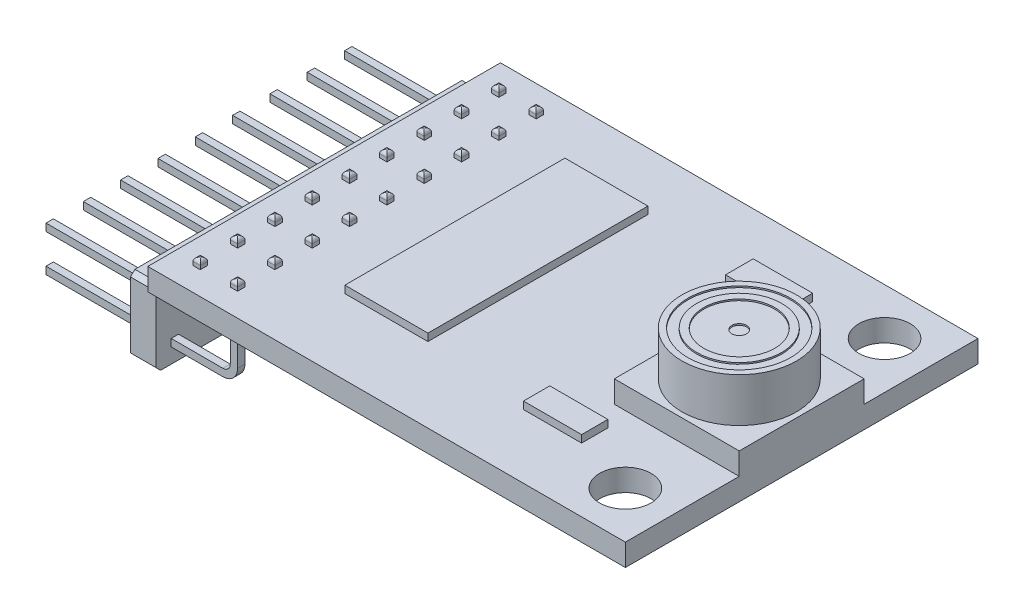
SolidWorks part; units mm, degrees
ref_plane "前视基准面" through (0, 0, 0) normal (0, 0, 1) x (1, 0, 0)
ref_plane "上视基准面" through (0, 0, 0) normal (0, 1, 0) x (1, 0, 0)
ref_plane "右视基准面" through (0, 0, 0) normal (1, 0, 0) x (0, 0, -1)
other "Configuration Table"
sketch "草图1" plane through (0, 0, 0) normal (0, 1, 0) x (1, 0, 0)
  line L0 (0, -12) -> (32.5, -12) construction
  line L1 (0, 0) -> (32.5, 0)
  line L2 (0, 0) -> (0, -24)
  line L3 (0, -24) -> (32.5, -24)
  line L4 (32.5, 0) -> (32.5, -24)
  circle A0 centre (29.32, -3.18) radius 1.75
  circle A1 centre (29.32, -20.82) radius 1.75
  dimension "D3" = 3.5
  dimension "D4" = 3.18
  dimension "D5" = 3.18
  dimension "D6" = 3.5
  dimension "D7" = 3.18
  dimension "D8" = 3.18
  dimension "D1" = 24
  dimension "D2" = 32.5
extrude "凸台-拉伸1" add sketch "草图1" along normal blind 1.5
sketch "草图2" plane through (0, 1.5, 0) normal (0, 1, 0) x (1, 0, 0)
  line L0 (0, -12) -> (32.5, -12) construction
  line L1 (0, 0) -> (0, -24) construction
  line L2 (32.5, -24) -> (32.5, 0) construction
  line L4 (24, -7.75) -> (32.5, -7.75)
  line L5 (24, -7.75) -> (24, -16.25)
  line L6 (24, -16.25) -> (32.5, -16.25)
  line L7 (32.5, -7.75) -> (32.5, -16.25)
  line L8 (24, -7.75) -> (32.5, -16.25) construction
  line L9 (24, -16.25) -> (32.5, -7.75) construction
  point P6 (28.25, -12)
  dimension "D1" = 8.5
  dimension "D2" = 8.5
extrude "凸台-拉伸2" add sketch "草图2" along normal blind 1.5
sketch "草图3" plane through (0, 3, 0) normal (0, 1, 0) x (1, 0, 0)
  line L0 (24, -12) -> (32.5, -12) construction
  line L1 (24, -7.75) -> (24, -16.25) construction
  line L2 (32.5, -16.25) -> (32.5, -7.75) construction
  line L3 (28.25, -7.75) -> (28.25, -16.25) construction
  line L4 (32.5, -7.75) -> (24, -7.75) construction
  line L5 (24, -16.25) -> (32.5, -16.25) construction
  circle A0 centre (28.25, -12) radius 3.9
  dimension "D1" = 7.8
extrude "凸台-拉伸3" add sketch "草图3" along normal blind 3
sketch "草图4" plane through (0, 0, 0) normal (0, -1, 0) x (1, 0, 0)
  line L0 (1.73, 0) -> (1.73, 24) construction
  line L1 (32.5, 0) -> (0, 0) construction
  line L2 (0, 24) -> (32.5, 24) construction
  line L3 (4.27, 0) -> (4.27, 24) construction
  line L4 (0, 0) -> (0, 24) construction
  line L5 (0, 12) -> (32.5, 12) construction
  line L6 (32.5, 24) -> (32.5, 0) construction
  line L7 (1.48, 14.79) -> (1.98, 14.79)
  line L8 (1.48, 12.25) -> (1.98, 12.25)
  line L9 (1.48, 12.25) -> (1.48, 11.75)
  line L10 (1.48, 11.75) -> (1.98, 11.75)
  line L11 (1.98, 12.25) -> (1.98, 11.75)
  line L12 (1.48, 12.25) -> (1.98, 11.75) construction
  line L13 (1.48, 11.75) -> (1.98, 12.25) construction
  line L14 (4.02, 12.25) -> (4.52, 12.25)
  line L15 (4.02, 12.25) -> (4.02, 11.75)
  line L16 (4.02, 11.75) -> (4.52, 11.75)
  line L17 (4.52, 12.25) -> (4.52, 11.75)
  line L18 (4.02, 12.25) -> (4.52, 11.75) construction
  line L19 (4.02, 11.75) -> (4.52, 12.25) construction
  line L20 (1.48, 14.79) -> (1.48, 14.29)
  line L21 (1.98, 14.79) -> (1.98, 14.29)
  line L22 (1.48, 14.29) -> (1.98, 14.29)
  line L23 (4.02, 14.29) -> (4.52, 14.29)
  line L24 (4.52, 14.79) -> (4.52, 14.29)
  line L25 (4.02, 14.79) -> (4.02, 14.29)
  line L26 (4.02, 14.79) -> (4.52, 14.79)
  line L27 (1.48, 17.33) -> (1.98, 17.33)
  line L28 (1.48, 17.33) -> (1.48, 16.83)
  line L29 (1.98, 17.33) -> (1.98, 16.83)
  line L30 (1.48, 16.83) -> (1.98, 16.83)
  line L31 (4.02, 16.83) -> (4.52, 16.83)
  line L32 (4.52, 17.33) -> (4.52, 16.83)
  line L33 (4.02, 17.33) -> (4.02, 16.83)
  line L34 (4.02, 17.33) -> (4.52, 17.33)
  line L35 (1.48, 19.87) -> (1.98, 19.87)
  line L36 (1.48, 19.87) -> (1.48, 19.37)
  line L37 (1.98, 19.87) -> (1.98, 19.37)
  line L38 (1.48, 19.37) -> (1.98, 19.37)
  line L39 (4.02, 19.37) -> (4.52, 19.37)
  line L40 (4.52, 19.87) -> (4.52, 19.37)
  line L41 (4.02, 19.87) -> (4.02, 19.37)
  line L42 (4.02, 19.87) -> (4.52, 19.87)
  line L43 (1.48, 22.41) -> (1.98, 22.41)
  line L44 (1.48, 22.41) -> (1.48, 21.91)
  line L45 (1.98, 22.41) -> (1.98, 21.91)
  line L46 (1.48, 21.91) -> (1.98, 21.91)
  line L47 (4.02, 21.91) -> (4.52, 21.91)
  line L48 (4.52, 22.41) -> (4.52, 21.91)
  line L49 (4.02, 22.41) -> (4.02, 21.91)
  line L50 (4.02, 22.41) -> (4.52, 22.41)
  line L51 (1.48, 4.63) -> (1.98, 4.63)
  line L52 (1.48, 4.63) -> (1.48, 4.13)
  line L53 (1.98, 4.63) -> (1.98, 4.13)
  line L54 (1.48, 4.13) -> (1.98, 4.13)
  line L55 (4.02, 4.13) -> (4.52, 4.13)
  line L56 (4.52, 4.63) -> (4.52, 4.13)
  line L57 (4.02, 4.63) -> (4.02, 4.13)
  line L58 (4.02, 4.63) -> (4.52, 4.63)
  line L59 (1.48, 7.17) -> (1.98, 7.17)
  line L60 (1.48, 7.17) -> (1.48, 6.67)
  line L61 (1.98, 7.17) -> (1.98, 6.67)
  line L62 (1.48, 6.67) -> (1.98, 6.67)
  line L63 (4.02, 6.67) -> (4.52, 6.67)
  line L64 (4.52, 7.17) -> (4.52, 6.67)
  line L65 (4.02, 7.17) -> (4.02, 6.67)
  line L66 (4.02, 7.17) -> (4.52, 7.17)
  line L67 (1.48, 9.71) -> (1.98, 9.71)
  line L68 (1.48, 9.71) -> (1.48, 9.21)
  line L69 (1.98, 9.71) -> (1.98, 9.21)
  line L70 (1.48, 9.21) -> (1.98, 9.21)
  line L71 (4.02, 9.21) -> (4.52, 9.21)
  line L72 (4.52, 9.71) -> (4.52, 9.21)
  line L73 (4.02, 9.71) -> (4.02, 9.21)
  line L74 (4.02, 9.71) -> (4.52, 9.71)
  line L83 (1.48, 2.09) -> (1.98, 2.09)
  line L84 (1.48, 2.09) -> (1.48, 1.59)
  line L85 (1.98, 2.09) -> (1.98, 1.59)
  line L86 (1.48, 1.59) -> (1.98, 1.59)
  line L87 (4.02, 1.59) -> (4.52, 1.59)
  line L88 (4.52, 2.09) -> (4.52, 1.59)
  line L89 (4.02, 2.09) -> (4.02, 1.59)
  line L90 (4.02, 2.09) -> (4.52, 2.09)
  line L91 (1.48, 12.25) -> (1.98, 12.25) [skipped]
  line L92 (1.48, 11.75) -> (1.98, 11.75) [skipped]
  line L93 (1.48, 12.25) -> (1.48, 11.75) [skipped]
  line L94 (1.98, 12.25) -> (1.98, 11.75) [skipped]
  line L95 (4.02, 12.25) -> (4.52, 12.25) [skipped]
  line L96 (4.02, 12.25) -> (4.02, 11.75) [skipped]
  line L97 (4.02, 11.75) -> (4.52, 11.75) [skipped]
  line L98 (4.52, 12.25) -> (4.52, 11.75) [skipped]
  point P14 (1.73, 12)
  point P19 (4.27, 12)
  dimension "D1" = 1.73
  dimension "D2" = 2.54
  dimension "D3" = 0.5
  dimension "D4" = 0.5
  dimension "D5" = 0.5
  dimension "D6" = 0.5
  dimension "D9" = 2.54
  dimension "D10" = 2.54
  dimension "D7" = 5
  dimension "D8" = 2
extrude "凸台-拉伸4" add sketch "草图4" along normal blind 1.5 and the other way blind 2 contours L44 L46 L45 L43 | L36 L38 L37 L35 | L28 L30 L29 L27 | L20 L22 L21 L7 | L9 L11 L8 | L9 L10 L11 | L68 L70 L69 L67 | L60 L62 L61 L59 | L52 L54 L53 L51 | L84 L86 L85 L83 region at (1.73, 0, 14.54) region at (1.73, 0, 12) region at (1.73, 0, 17.08) region at (1.73, 0, 19.62) region at (1.73, 0, 22.16) region at (1.73, 0, 4.38) region at (1.73, 0, 6.92) region at (1.73, 0, 9.46) region at (1.73, 0, 1.84)
extrude "凸台-拉伸5" add sketch "草图4<3>" along normal blind 4.04 and the other way blind 2 contours L50 L49 L47 L48 | L42 L41 L39 L40 | L34 L33 L31 L32 | L26 L25 L23 L24 | L15 L17 L14 | L15 L16 L17 | L74 L73 L71 L72 | L66 L65 L63 L64 | L58 L57 L55 L56 | L90 L89 L87 L88 region at (4.27, 0, 12) region at (4.27, 0, 14.54) region at (4.27, 0, 17.08) region at (4.27, 0, 19.62) region at (4.27, 0, 22.16) region at (4.27, 0, 4.38) region at (4.27, 0, 6.92) region at (4.27, 0, 9.46) region at (4.27, 0, 1.84)
sketch "草图4<3>" plane through (0, 0, 0) normal (0, -1, 0) x (1, 0, 0) same geometry as "草图4"
fillet "圆角1" radius 0.25 72 edges at (1.73, 2, 1.59) (1.98, 2, 1.84) (1.73, 2, 2.09) (1.48, 2, 1.84) (4.02, 2, 1.84) (4.27, 2, 1.59) (4.52, 2, 1.84) (4.27, 2, 2.09) (4.02, 2, 4.38) (4.27, 2, 4.13) (4.52, 2, 4.38) (4.27, 2, 4.63) (1.73, 2, 4.13) (1.98, 2, 4.38) (1.73, 2, 4.63) (1.48, 2, 4.38) (1.73, 2, 6.67) (1.98, 2, 6.92) (1.73, 2, 7.17) (1.48, 2, 6.92) (4.02, 2, 6.92) (4.27, 2, 6.67) (4.52, 2, 6.92) (4.27, 2, 7.17) (4.02, 2, 9.46) (4.27, 2, 9.21) (4.52, 2, 9.46) (4.27, 2, 9.71) (1.73, 2, 9.21) (1.98, 2, 9.46) (1.73, 2, 9.71) (1.48, 2, 9.46) (1.73, 2, 12.25) (1.48, 2, 12) (1.73, 2, 11.75) (1.98, 2, 12) (4.27, 2, 12.25) (4.02, 2, 12) (4.27, 2, 11.75) (4.52, 2, 12) (1.73, 2, 14.29) (1.98, 2, 14.54) (1.73, 2, 14.79) (1.48, 2, 14.54) (4.02, 2, 14.54) (4.27, 2, 14.29) (4.52, 2, 14.54) (4.27, 2, 14.79) (1.73, 2, 16.83) (1.98, 2, 17.08) (1.73, 2, 17.33) (1.48, 2, 17.08) (4.02, 2, 17.08) (4.27, 2, 16.83) (4.52, 2, 17.08) (4.27, 2, 17.33) (4.02, 2, 19.62) (4.27, 2, 19.37) (4.52, 2, 19.62) (4.27, 2, 19.87) (1.73, 2, 19.37) (1.98, 2, 19.62) (1.73, 2, 19.87) (1.48, 2, 19.62) (1.73, 2, 21.91) (1.98, 2, 22.16) (1.73, 2, 22.41) (1.48, 2, 22.16) (4.02, 2, 22.16) (4.27, 2, 21.91) (4.52, 2, 22.16) (4.27, 2, 22.41)
sketch "草图5" plane through (0, 1.5, 0) normal (0, 1, 0) x (1, 0, 0)
  line L1 (8.3105, -3.924) -> (13.9614, -3.924)
  line L2 (8.3105, -3.924) -> (8.3105, -18.8988)
  line L3 (8.3105, -18.8988) -> (13.9614, -18.8988)
  line L4 (13.9614, -3.924) -> (13.9614, -18.8988)
  line L5 (20.653, -3.4531) -> (24.7027, -3.4531)
  line L6 (20.653, -3.4531) -> (20.653, -5.3367)
  line L7 (20.653, -5.3367) -> (24.7027, -5.3367)
  line L8 (24.7027, -3.4531) -> (24.7027, -5.3367)
  line L9 (21.218, -17.8628) -> (25.1736, -17.8628)
  line L10 (21.218, -17.8628) -> (21.218, -19.6522)
  line L11 (21.218, -19.6522) -> (25.1736, -19.6522)
  line L12 (25.1736, -17.8628) -> (25.1736, -19.6522)
extrude "凸台-拉伸6" add sketch "草图5" along normal blind 0.5
sketch "草图6" plane through (0, 0, 0) normal (0, -1, 0) x (1, 0, 0)
  line L1 (10.4704, 20.7091) -> (12.1055, 20.7091)
  line L2 (10.4704, 20.7091) -> (10.4704, 19.778)
  line L3 (10.4704, 19.778) -> (12.1055, 19.778)
  line L4 (12.1055, 20.7091) -> (12.1055, 19.778)
  line L5 (10.7202, 18.1202) -> (12.1055, 18.1202)
  line L6 (10.7202, 18.1202) -> (10.7202, 17.3481)
  line L7 (10.7202, 17.3481) -> (12.1055, 17.3481)
  line L8 (12.1055, 18.1202) -> (12.1055, 17.3481)
  line L9 (10.4704, 16.0764) -> (12.537, 16.0764)
  line L10 (10.4704, 16.0764) -> (10.4704, 15.168)
  line L11 (10.4704, 15.168) -> (12.537, 15.168)
  line L12 (12.537, 16.0764) -> (12.537, 15.168)
  line L13 (10.7202, 14.3504) -> (12.537, 14.3504)
  line L14 (10.7202, 14.3504) -> (10.7202, 13.056)
  line L15 (10.7202, 13.056) -> (12.537, 13.056)
  line L16 (12.537, 14.3504) -> (12.537, 13.056)
  line L17 (10.4704, 12.1249) -> (12.537, 12.1249)
  line L18 (10.4704, 12.1249) -> (10.4704, 10.8986)
  line L19 (10.4704, 10.8986) -> (12.537, 10.8986)
  line L20 (12.537, 12.1249) -> (12.537, 10.8986)
  line L21 (16.1932, 16.0764) -> (19.6905, 16.0764)
  line L22 (16.1932, 16.0764) -> (16.1932, 11.3528)
  line L23 (16.1932, 11.3528) -> (19.6905, 11.3528)
  line L24 (19.6905, 16.0764) -> (19.6905, 11.3528)
  line L25 (15.9434, 20.2436) -> (17.5558, 20.2436)
  line L26 (15.9434, 20.2436) -> (15.9434, 18.3473)
  line L27 (15.9434, 18.3473) -> (17.5558, 18.3473)
  line L28 (17.5558, 20.2436) -> (17.5558, 18.3473)
  line L33 (8.472, 9.2408) -> (9.2895, 9.2408)
  line L34 (8.472, 9.2408) -> (8.472, 7.2878)
  line L35 (8.472, 7.2878) -> (9.2895, 7.2878)
  line L36 (9.2895, 9.2408) -> (9.2895, 7.2878)
  line L37 (10.2206, 8.9001) -> (11.8784, 8.9001)
  line L38 (10.2206, 8.9001) -> (10.2206, 7.2878)
  line L39 (10.2206, 7.2878) -> (11.8784, 7.2878)
  line L40 (11.8784, 8.9001) -> (11.8784, 7.2878)
  line L41 (13.0593, 9.2408) -> (14.7398, 9.2408)
  line L42 (13.0593, 9.2408) -> (13.0593, 6.8563)
  line L43 (13.0593, 6.8563) -> (14.7398, 6.8563)
  line L44 (14.7398, 9.2408) -> (14.7398, 6.8563)
  line L45 (15.5574, 9.5133) -> (16.9881, 9.5133)
  line L46 (15.5574, 9.5133) -> (15.5574, 7.1061)
  line L47 (15.5574, 7.1061) -> (16.9881, 7.1061)
  line L48 (16.9881, 9.5133) -> (16.9881, 7.1061)
  line L49 (17.9419, 9.2408) -> (19.6905, 9.2408)
  line L50 (17.9419, 9.2408) -> (17.9419, 6.8563)
  line L51 (17.9419, 6.8563) -> (19.6905, 6.8563)
  line L52 (19.6905, 9.2408) -> (19.6905, 6.8563)
  line L53 (20.7124, 9.5133) -> (22.6427, 9.5133)
  line L54 (20.7124, 9.5133) -> (20.7124, 6.4702)
  line L55 (20.7124, 6.4702) -> (22.6427, 6.4702)
  line L56 (22.6427, 9.5133) -> (22.6427, 6.4702)
  line L57 (23.6874, 9.2408) -> (25.5041, 9.2408)
  line L58 (23.6874, 9.2408) -> (23.6874, 6.8563)
  line L59 (23.6874, 6.8563) -> (25.5041, 6.8563)
  line L60 (25.5041, 9.2408) -> (25.5041, 6.8563)
  line L65 (8.472, 5.7208) -> (9.4485, 5.7208)
  line L66 (8.472, 5.7208) -> (8.472, 3.8132)
  line L67 (8.472, 3.8132) -> (9.4485, 3.8132)
  line L68 (9.4485, 5.7208) -> (9.4485, 3.8132)
  line L69 (10.0617, 5.7208) -> (11.5037, 5.7208)
  line L70 (10.0617, 5.7208) -> (10.0617, 3.8132)
  line L71 (10.0617, 3.8132) -> (11.5037, 3.8132)
  line L72 (11.5037, 5.7208) -> (11.5037, 3.8132)
  line L73 (11.8784, 5.7208) -> (13.4454, 5.7208)
  line L74 (11.8784, 5.7208) -> (11.8784, 3.8132)
  line L75 (11.8784, 3.8132) -> (13.4454, 3.8132)
  line L76 (13.4454, 5.7208) -> (13.4454, 3.8132)
  line L77 (14.1494, 5.7208) -> (15.9434, 5.7208)
  line L78 (14.1494, 5.7208) -> (14.1494, 3.8132)
  line L79 (14.1494, 3.8132) -> (15.9434, 3.8132)
  line L80 (15.9434, 5.7208) -> (15.9434, 3.8132)
  line L81 (16.4203, 5.5618) -> (17.5558, 5.5618)
  line L82 (16.4203, 5.5618) -> (16.4203, 4.1539)
  line L83 (16.4203, 4.1539) -> (17.5558, 4.1539)
  line L84 (17.5558, 5.5618) -> (17.5558, 4.1539)
  line L85 (8.4899, 1.4514) -> (9.6983, 1.4514)
  line L86 (8.4899, 1.4514) -> (8.4899, 2.3598)
  line L87 (8.4899, 2.3598) -> (9.6983, 2.3598)
  line L88 (9.6983, 1.4514) -> (9.6983, 2.3598)
  line L89 (11.8784, 3.359) -> (12.6619, 3.359)
  line L90 (11.8784, 3.359) -> (11.8784, 1.4514)
  line L91 (11.8784, 1.4514) -> (12.6619, 1.4514)
  line L92 (12.6619, 3.359) -> (12.6619, 1.4514)
  line L93 (13.7406, 3.1319) -> (14.7398, 3.1319)
  line L94 (13.7406, 3.1319) -> (13.7406, 1.4514)
  line L95 (13.7406, 1.4514) -> (14.7398, 1.4514)
  line L96 (14.7398, 3.1319) -> (14.7398, 1.4514)
  line L97 (16.1932, 3.1319) -> (17.9419, 3.1319)
  line L98 (16.1932, 3.1319) -> (16.1932, 1.6785)
  line L99 (16.1932, 1.6785) -> (17.9419, 1.6785)
  line L100 (17.9419, 3.1319) -> (17.9419, 1.6785)
  line L101 (21.6776, 5.0849) -> (23.6874, 5.0849)
  line L102 (21.6776, 5.0849) -> (21.6776, 4.1539)
  line L103 (21.6776, 4.1539) -> (23.6874, 4.1539)
  line L104 (23.6874, 5.0849) -> (23.6874, 4.1539)
  line L105 (20.9622, 2.4052) -> (23.9826, 2.4052)
  line L106 (20.9622, 2.4052) -> (20.9622, 1.6785)
  line L107 (20.9622, 1.6785) -> (23.9826, 1.6785)
  line L108 (23.9826, 2.4052) -> (23.9826, 1.6785)
extrude "凸台-拉伸7" add sketch "草图6" along normal blind 1
sketch "草图8" plane through (4.02, 0, 0) normal (-1, 0, 0) x (0, 0, 1)
  line L0 (22.41, 0) -> (22.41, -4.04) construction
  line L1 (21.91, -4.04) -> (22.41, -4.04)
  line L2 (21.91, -4.04) -> (21.91, -3.54)
  line L3 (21.91, -3.54) -> (22.41, -3.54)
  line L4 (22.41, -4.04) -> (22.41, -3.54)
  line L5 (19.37, -4.04) -> (19.87, -4.04)
  line L6 (19.37, -4.04) -> (19.37, -3.54)
  line L7 (19.37, -3.54) -> (19.87, -3.54)
  line L8 (19.87, -4.04) -> (19.87, -3.54)
  line L9 (16.83, -4.04) -> (17.33, -4.04)
  line L10 (16.83, -4.04) -> (16.83, -3.54)
  line L11 (16.83, -3.54) -> (17.33, -3.54)
  line L12 (17.33, -4.04) -> (17.33, -3.54)
  line L13 (14.29, -4.04) -> (14.79, -4.04)
  line L14 (14.29, -4.04) -> (14.29, -3.54)
  line L15 (14.29, -3.54) -> (14.79, -3.54)
  line L16 (14.79, -4.04) -> (14.79, -3.54)
  line L17 (11.75, -4.04) -> (12.25, -4.04)
  line L18 (11.75, -4.04) -> (11.75, -3.54)
  line L19 (11.75, -3.54) -> (12.25, -3.54)
  line L20 (12.25, -4.04) -> (12.25, -3.54)
  line L21 (9.21, -4.04) -> (9.71, -4.04)
  line L22 (9.21, -4.04) -> (9.21, -3.54)
  line L23 (9.21, -3.54) -> (9.71, -3.54)
  line L24 (9.71, -4.04) -> (9.71, -3.54)
  line L25 (6.67, -4.04) -> (7.17, -4.04)
  line L26 (6.67, -4.04) -> (6.67, -3.54)
  line L27 (6.67, -3.54) -> (7.17, -3.54)
  line L28 (7.17, -4.04) -> (7.17, -3.54)
  line L29 (4.13, -4.04) -> (4.63, -4.04)
  line L30 (4.13, -4.04) -> (4.13, -3.54)
  line L31 (4.13, -3.54) -> (4.63, -3.54)
  line L32 (4.63, -4.04) -> (4.63, -3.54)
  line L33 (1.59, -4.04) -> (2.09, -4.04)
  line L34 (1.59, -4.04) -> (1.59, -3.54)
  line L35 (1.59, -3.54) -> (2.09, -3.54)
  line L36 (2.09, -4.04) -> (2.09, -3.54)
  dimension "D1" = 0.5
  dimension "D2" = 9
extrude "凸台-拉伸8" add sketch "草图8" along normal blind 12.54
sketch "草图9" plane through (1.48, 0, 0) normal (-1, 0, 0) x (0, 0, 1)
  line L0 (2.09, 0) -> (2.09, -1.5) construction
  line L1 (1.59, -1.5) -> (2.09, -1.5)
  line L2 (1.59, -1.5) -> (1.59, -1)
  line L3 (1.59, -1) -> (2.09, -1)
  line L4 (2.09, -1.5) -> (2.09, -1)
  line L5 (4.13, -1.5) -> (4.63, -1.5)
  line L6 (4.13, -1.5) -> (4.13, -1)
  line L7 (4.13, -1) -> (4.63, -1)
  line L8 (4.63, -1.5) -> (4.63, -1)
  line L9 (6.67, -1.5) -> (7.17, -1.5)
  line L10 (6.67, -1.5) -> (6.67, -1)
  line L11 (6.67, -1) -> (7.17, -1)
  line L12 (7.17, -1.5) -> (7.17, -1)
  line L13 (9.21, -1.5) -> (9.71, -1.5)
  line L14 (9.21, -1.5) -> (9.21, -1)
  line L15 (9.21, -1) -> (9.71, -1)
  line L16 (9.71, -1.5) -> (9.71, -1)
  line L17 (11.75, -1.5) -> (12.25, -1.5)
  line L18 (11.75, -1.5) -> (11.75, -1)
  line L19 (11.75, -1) -> (12.25, -1)
  line L20 (12.25, -1.5) -> (12.25, -1)
  line L21 (14.29, -1.5) -> (14.79, -1.5)
  line L22 (14.29, -1.5) -> (14.29, -1)
  line L23 (14.29, -1) -> (14.79, -1)
  line L24 (14.79, -1.5) -> (14.79, -1)
  line L25 (16.83, -1.5) -> (17.33, -1.5)
  line L26 (16.83, -1.5) -> (16.83, -1)
  line L27 (16.83, -1) -> (17.33, -1)
  line L28 (17.33, -1.5) -> (17.33, -1)
  line L29 (19.37, -1.5) -> (19.87, -1.5)
  line L30 (19.37, -1.5) -> (19.37, -1)
  line L31 (19.37, -1) -> (19.87, -1)
  line L32 (19.87, -1.5) -> (19.87, -1)
  line L33 (21.91, -1.5) -> (22.41, -1.5)
  line L34 (21.91, -1.5) -> (21.91, -1)
  line L35 (21.91, -1) -> (22.41, -1)
  line L36 (22.41, -1.5) -> (22.41, -1)
  dimension "D1" = 0.5
  dimension "D2" = 9
extrude "凸台-拉伸9" add sketch "草图9" along normal blind 10
fillet "圆角3" radius 0.5 18 edges at (1.48, -1, 1.84) (1.48, -1, 4.38) (1.48, -1, 6.92) (1.48, -1, 9.46) (1.48, -1, 12) (1.48, -1, 14.54) (1.48, -1, 17.08) (1.48, -1, 19.62) (1.48, -1, 22.16) (4.02, -3.54, 22.16) (4.02, -3.54, 19.62) (4.02, -3.54, 17.08) (4.02, -3.54, 14.54) (4.02, -3.54, 12) (4.02, -3.54, 9.46) (4.02, -3.54, 6.92) (4.02, -3.54, 4.38) (4.02, -3.54, 1.84)
fillet "圆角4" radius 1 18 edges at (4.52, -4.04, 22.16) (1.98, -1.5, 22.16) (4.52, -4.04, 19.62) (1.98, -1.5, 19.62) (1.98, -1.5, 17.08) (4.52, -4.04, 17.08) (4.52, -4.04, 14.54) (1.98, -1.5, 14.54) (1.98, -1.5, 12) (4.52, -4.04, 12) (4.52, -4.04, 9.46) (1.98, -1.5, 9.46) (1.98, -1.5, 6.92) (4.52, -4.04, 6.92) (4.52, -4.04, 4.38) (1.98, -1.5, 4.38) (4.52, -4.04, 1.84) (1.98, -1.5, 1.84)
sketch "草图10" plane through (0, -1, 0) normal (0, 1, 0) x (1, 0, 0)
  line L0 (0, 0) -> (0, -24) construction
  line L1 (-1.75, -0.57) -> (0, -0.57)
  line L2 (-1.75, -0.57) -> (-1.75, -23.43)
  line L3 (-1.75, -23.43) -> (0, -23.43)
  line L4 (0, -0.57) -> (0, -23.43)
  line L5 (-8.52, -2.09) -> (-8.52, -1.59) construction
  line L6 (-8.52, -22.41) -> (-8.52, -21.91) construction
  point P8 (-8.52, -1.84)
  point P11 (-8.52, -22.16)
  dimension "D1" = 1.75
  dimension "D2" = 1.27
  dimension "D3" = 1.27
extrude "凸台-拉伸10" add sketch "草图10" along normal blind 1.02 and the other way blind 4.06
chamfer "倒角1" distance 0.3 angle 45 4 edges at (-0.875, 0.02, 23.43) (-0.875, -5.06, 23.43) (-0.875, -5.06, 0.57) (-0.875, 0.02, 0.57)
sketch "草图11" plane through (0, 6, 0) normal (0, 1, 0) x (1, 0, 0)
  circle A0 centre (28.25, -12) radius 3.5
  dimension "D1" = 7
extrude "切除-拉伸1" cut sketch "草图11" against normal blind 0.1
sketch "草图12" plane through (0, 5.9, 0) normal (0, 1, 0) x (1, 0, 0)
  circle A0 centre (28.25, -12) radius 0.5
  dimension "D1" = 1
extrude "切除-拉伸2" cut sketch "草图12" against normal blind 0.1
sketch "草图13" plane through (0, 5.9, 0) normal (0, 1, 0) x (1, 0, 0)
  circle A0 centre (28.25, -12) radius 2.8925
  circle A1 centre (28.25, -12) radius 2.4107
extrude "凸台-拉伸11" add sketch "草图13" along normal blind 0.1
